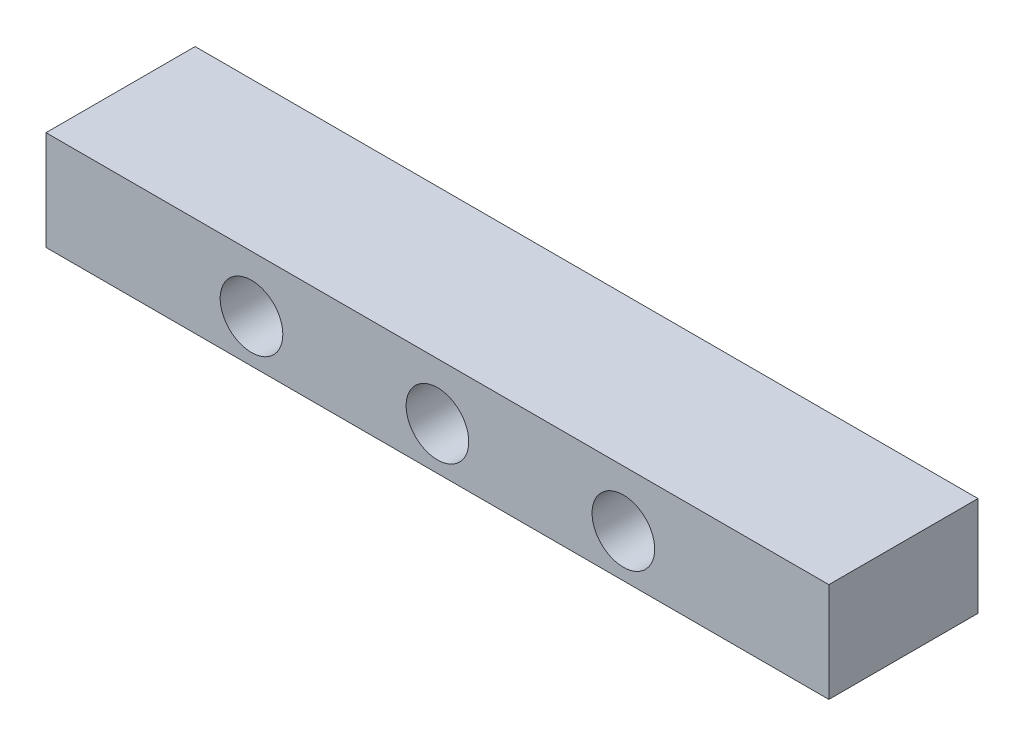
SolidWorks part; units mm, degrees
ref_plane "Front Plane" through (0, 0, 0) normal (0, 0, 1) x (1, 0, 0)
ref_plane "Top Plane" through (0, 0, 0) normal (0, 1, 0) x (1, 0, 0)
ref_plane "Right Plane" through (0, 0, 0) normal (1, 0, 0) x (0, 0, -1)
sketch "Sketch1" plane through (0, 0, 0) normal (0, 1, 0) x (1, 0, 0)
  line L1 (0, 0) -> (400, 0)
  line L2 (0, 0) -> (0, 76.2)
  line L3 (0, 76.2) -> (400, 76.2)
  line L4 (400, 0) -> (400, 76.2)
  dimension "D1" = 400
  dimension "D2" = 76.2
extrude "Boss-Extrude1" add sketch "Sketch1" along normal blind 50.8
sketch "Sketch2" plane through (0, 0, 0) normal (0, 0, 1) x (1, 0, 0)
  line L0 (105, 22) -> (200, 22)
  line L1 (0, 0) -> (105, 0)
  line L2 (0, 0) -> (0, 22)
  line L3 (0, 22) -> (105, 22)
  line L4 (105, 0) -> (105, 22)
  line L5 (200, 22) -> (295, 22)
  circle A0 centre (105, 22) radius 16
  circle A1 centre (200, 22) radius 16
  circle A2 centre (295, 22) radius 16
  dimension "D1" = 105
  dimension "D2" = 22
  dimension "D3" = 95
  dimension "D4" = 95
extrude "Cut-Extrude1" cut sketch "Sketch2" against normal blind 76.2 contours A0 | A1 | A2
